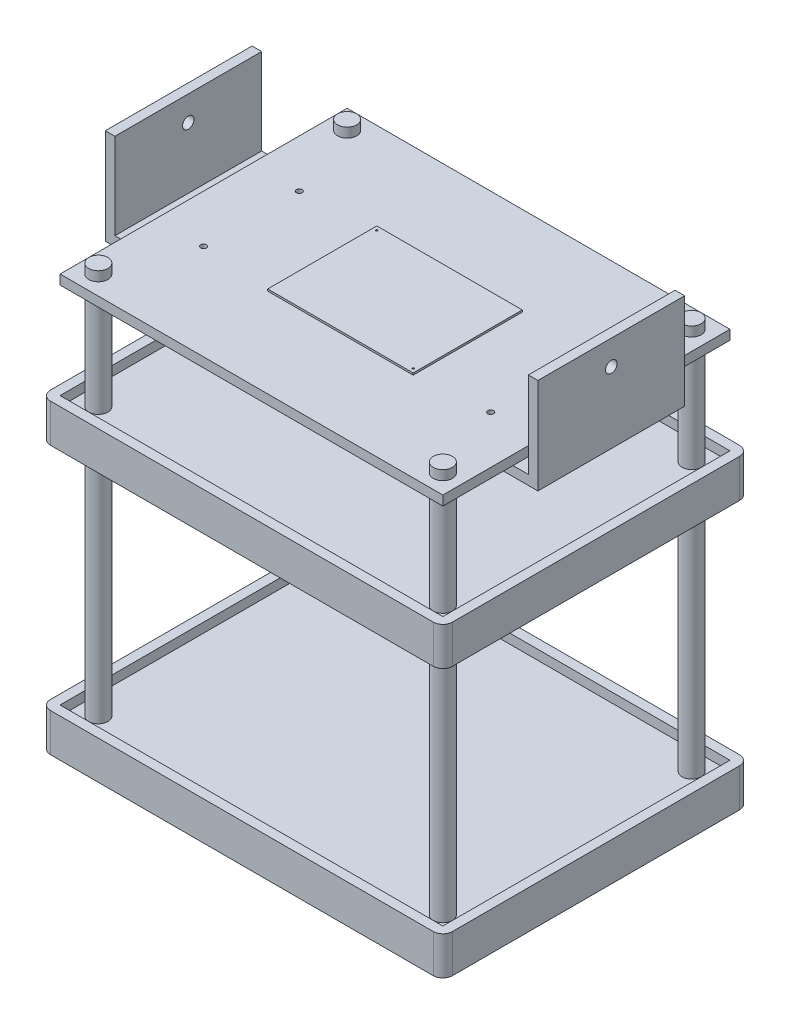
SolidWorks part; units mm, degrees
ref_plane "Front Plane" through (0, 0, 0) normal (0, 0, 1) x (1, 0, 0)
ref_plane "Top Plane" through (0, 0, 0) normal (0, 1, 0) x (1, 0, 0)
ref_plane "Right Plane" through (0, 0, 0) normal (1, 0, 0) x (0, 0, -1)
sketch "Sketch1" plane through (0, 0, 0) normal (0, 1, 0) x (1, 0, 0)
  line L1 (-100, 75) -> (100, 75)
  line L2 (-100, 75) -> (-100, -75)
  line L3 (-100, -75) -> (100, -75)
  line L4 (100, 75) -> (100, -75)
  line L5 (-100, 75) -> (100, -75) construction
  line L6 (-100, -75) -> (100, 75) construction
  point P0 (0, 0)
  dimension "D1" = 200
  dimension "D2" = 150
extrude "Boss-Extrude1" add sketch "Sketch1" along normal blind 5
sketch "Sketch2" plane through (0, 5, 0) normal (0, 1, 0) x (1, 0, 0)
  line L0 (-100, 75) -> (-100, -75) construction
  line L1 (100, 75) -> (-100, 75) construction
  line L2 (0, 73.0671) -> (0, 83.6614) construction
  line L3 (0, 83.6614) -> (0, -94.4748) construction
  line L4 (-110.8687, 0) -> (113.9791, 0) construction
  circle A0 centre (-90, 65) radius 5
  circle A1 centre (90, 65) radius 5
  circle A2 centre (90, -65) radius 5
  circle A3 centre (-90, -65) radius 5
  dimension "D1" = 10
  dimension "D2" = 10
  dimension "D3" = 10
extrude "Cut-Extrude1" cut sketch "Sketch2" against normal blind 10
ref_plane "Plane1" through (0, 140, 0) normal (0, 1, 0) x (1, 0, 0)
sketch "Sketch3" plane through (0, 140, 0) normal (0, 1, 0) x (1, 0, 0)
  line L1 (-100, 75) -> (100, 75)
  line L2 (-100, 75) -> (-100, -75)
  line L3 (-100, -75) -> (100, -75)
  line L4 (100, 75) -> (100, -75)
  line L5 (-100, 75) -> (100, -75) construction
  line L6 (-100, -75) -> (100, 75) construction
  circle A0 centre (-90, 65) radius 5
  circle A1 centre (90, 65) radius 5
  circle A2 centre (-90, -65) radius 5
  circle A3 centre (90, -65) radius 5
  point P0 (0, 0)
extrude "Boss-Extrude2" add sketch "Sketch3" along normal blind 5 separate body
ref_plane "Plane4" through (0, 200, 0) normal (0, 1, 0) x (1, 0, 0)
sketch "Sketch4" plane through (0, 200, 0) normal (0, 1, 0) x (1, 0, 0)
  line L1 (-100, 75) -> (100, 75)
  line L2 (-100, 75) -> (-100, -75)
  line L3 (-100, -75) -> (100, -75)
  line L4 (100, 75) -> (100, -75)
  line L5 (-100, 75) -> (100, -75) construction
  line L6 (-100, -75) -> (100, 75) construction
  circle A0 centre (-90, 65) radius 5
  circle A1 centre (90, 65) radius 5
  circle A2 centre (90, -65) radius 5
  circle A3 centre (-90, -65) radius 5
  point P1 (0, 0)
extrude "Boss-Extrude3" add sketch "Sketch4" along normal blind 5 separate body
sketch "Sketch5" plane through (0, 205, 0) normal (0, 1, 0) x (1, 0, 0)
  circle A0 centre (-90, -65) radius 5
sketch "Sketch17" plane through (0, 200, 0) normal (0, -1, 0) x (1, 0, 0)
  circle A0 centre (-90, -65) radius 5.3637
sketch "Sketch21" plane through (0, 5, 0) normal (0, 1, 0) x (1, 0, 0)
  circle A0 centre (-90, -65) radius 5
  circle A1 centre (-90, 65) radius 5
  circle A2 centre (90, 65) radius 5
  circle A3 centre (90, -65) radius 5
  dimension "D1" = 10
  dimension "D2" = 10
  dimension "D3" = 10
  dimension "D4" = 10
extrude "Boss-Extrude13" add sketch "Sketch21" along normal blind 205
sketch "Sketch22" plane through (0, 5, 0) normal (0, 1, 0) x (1, 0, 0)
  circle A0 centre (-90, 65) radius 5
  circle A1 centre (-90, -65) radius 5
  circle A2 centre (90, -65) radius 5
  circle A3 centre (90, 65) radius 5
  dimension "D1" = 10
  dimension "D2" = 10
  dimension "D3" = 10
  dimension "D4" = 10
extrude "Boss-Extrude14" add sketch "Sketch22" against normal blind 15
sketch "Sketch23" plane through (0, 205, 0) normal (0, 1, 0) x (1, 0, 0)
  line L0 (-100, 75) -> (-100, -75) construction
  line L1 (-140.155, 0) -> (119.4256, 0) construction
  line L2 (0, -2.75) -> (0, 2.75) construction
  circle A0 centre (-75, 25) radius 1.5
  circle A1 centre (-75, -25) radius 1.5
  circle A2 centre (75, -25) radius 1.5
  circle A3 centre (75, 25) radius 1.5
  dimension "D1" = 3
  dimension "D2" = 25
  dimension "D3" = 25
extrude "Cut-Extrude2" cut sketch "Sketch23" against normal blind 10
sketch "Sketch27" plane through (0, 205, 0) normal (0, 1, 0) x (1, 0, 0)
  line L0 (-38, 28.5) -> (38, -28.5) construction
  line L5 (-38, -28.5) -> (38, 28.5) construction
  line L7 (-38, 28.5) -> (38, 28.5)
  line L8 (-38, 28.5) -> (-38, -28.5)
  line L9 (-38, -28.5) -> (38, -28.5)
  line L10 (38, 28.5) -> (38, -28.5)
  circle A0 centre (-36, 26.5) radius 0.5
  circle A1 centre (36, -26.5) radius 0.5
  point P0 (-6.164, -10.787)
  point P5 (0, 0)
  point P11 (0, 0)
  dimension "D3" = 1
  dimension "D6" = 1
  dimension "D1" = 57
  dimension "D2" = 76
  dimension "D4" = 2
  dimension "D5" = 2
  dimension "D7" = 2
  dimension "D8" = 2
extrude "Boss-Extrude16" add sketch "Sketch27" along normal blind 1 contours L8 L7 L10 L9
sketch "Sketch30" plane through (0, 206, 0) normal (0, 1, 0) x (1, 0, 0)
  line L0 (-38, 28.5) -> (-38, -28.5) construction
  line L1 (-38, 28.5) -> (38, 28.5) construction
  line L2 (38, 28.5) -> (38, -28.5) construction
  line L3 (-38, -28.5) -> (38, -28.5) construction
  circle A0 centre (-36, 26.5) radius 0.5
  circle A1 centre (36, -26.5) radius 0.5
  dimension "D1" = 1
  dimension "D4" = 1
  dimension "D2" = 2
  dimension "D3" = 2
  dimension "D5" = 2
  dimension "D6" = 2
extrude "Cut-Extrude3" cut sketch "Sketch30" against normal blind 30
sketch "Sketch35" plane through (0, 0, 0) normal (0, -1, 0) x (-1, 0, 0)
  line L1 (100, -75) -> (-100, -75)
  line L2 (100, -75) -> (100, 75)
  line L3 (100, 75) -> (-100, 75)
  line L4 (-100, -75) -> (-100, 75)
  line L5 (100, -75) -> (-100, 75) construction
  line L6 (100, 75) -> (-100, -75) construction
  line L7 (105, -80) -> (-105, -80)
  line L8 (105, -80) -> (105, 80)
  line L9 (105, 80) -> (-105, 80)
  line L10 (-105, -80) -> (-105, 80)
  line L11 (105, -80) -> (-105, 80) construction
  line L12 (105, 80) -> (-105, -80) construction
  point P0 (0, 0)
  point P6 (0, 0)
  dimension "D1" = 150
  dimension "D2" = 160
  dimension "D3" = 200
  dimension "D4" = 210
extrude "Boss-Extrude19" add sketch "Sketch35" along normal mid plane 20 separate body
fillet "Fillet4" radius 5 4 edges at (105, 0, 80) (105, 0, -80) (-105, 0, 80) (-105, 0, -80)
sketch "Sketch39" plane through (0, 140, 0) normal (0, -1, 0) x (1, 0, 0)
  line L1 (-100, 75) -> (100, 75)
  line L2 (-100, 75) -> (-100, -75)
  line L3 (-100, -75) -> (100, -75)
  line L4 (100, 75) -> (100, -75)
  line L5 (-100, 75) -> (100, -75) construction
  line L6 (-100, -75) -> (100, 75) construction
  line L7 (-105, 80) -> (105, 80)
  line L8 (-105, 80) -> (-105, -80)
  line L9 (-105, -80) -> (105, -80)
  line L10 (105, 80) -> (105, -80)
  line L11 (-105, 80) -> (105, -80) construction
  line L12 (-105, -80) -> (105, 80) construction
  point P0 (0, 0)
  point P6 (0, 0)
  dimension "D1" = 150
  dimension "D2" = 200
  dimension "D3" = 160
  dimension "D4" = 210
extrude "Boss-Extrude20" add sketch "Sketch39" along normal mid plane 20 separate body
fillet "Fillet5" radius 5 4 edges at (105, 140, 80) (105, 140, -80) (-105, 140, -80) (-105, 140, 80)
sketch "Sketch42" plane through (0, 200, 0) normal (0, -1, 0) x (1, 0, 0)
  line L1 (-7.5, 10) -> (7.5, 10)
  line L2 (-7.5, 10) -> (-7.5, -10)
  line L3 (-7.5, -10) -> (7.5, -10)
  line L4 (7.5, 10) -> (7.5, -10)
  line L5 (-7.5, 10) -> (7.5, -10) construction
  line L6 (-7.5, -10) -> (7.5, 10) construction
  line L7 (-70.7403, -17.1967) -> (-45.7403, -17.1967)
  line L8 (-70.7403, -17.1967) -> (-70.7403, 32.8033)
  line L9 (-70.7403, 32.8033) -> (-45.7403, 32.8033)
  line L10 (-45.7403, -17.1967) -> (-45.7403, 32.8033)
  line L11 (-70.7403, -17.1967) -> (-45.7403, 32.8033) construction
  line L12 (-70.7403, 32.8033) -> (-45.7403, -17.1967) construction
  line L13 (15.7, 23.8618) -> (59, 23.8618)
  line L14 (15.7, 23.8618) -> (15.7, -19.4382)
  line L15 (15.7, -19.4382) -> (59, -19.4382)
  line L16 (59, 23.8618) -> (59, -19.4382)
  line L17 (15.7, 23.8618) -> (59, -19.4382) construction
  line L18 (15.7, -19.4382) -> (59, 23.8618) construction
  point P0 (0, 0)
  point P6 (-58.2403, 7.8033)
  point P11 (37.35, 2.2118)
  dimension "D1" = 20
  dimension "D2" = 15
  dimension "D3" = 50
  dimension "D4" = 25
  dimension "D5" = 43.3
  dimension "D6" = 43.3
  dimension "D7" = 8.2
extrude "Boss-Extrude23" add sketch "Sketch42" along normal blind 1
sketch "Sketch46" plane through (0, 200, 0) normal (0, -1, 0) x (-1, 0, 0)
  line L0 (-196.0871, 0) -> (303.0775, 0) construction
  line L5 (100, -75) -> (100, 75) construction
  line L6 (0, 82.5) -> (0, -82.5) construction
  line L7 (-108, 38.3353) -> (-108, -38.3353)
  line L8 (78, 38.3353) -> (108, 38.3353)
  line L9 (78, 38.3353) -> (78, -38.3353)
  line L10 (78, -38.3353) -> (108, -38.3353)
  line L11 (108, 38.3353) -> (108, -38.3353)
  line L12 (78, 38.3353) -> (108, -38.3353) construction
  line L13 (78, -38.3353) -> (108, 38.3353) construction
  line L14 (-78, -38.3353) -> (-108, -38.3353)
  line L15 (-78, 38.3353) -> (-78, -38.3353)
  line L16 (-78, 38.3353) -> (-108, 38.3353)
  point P0 (122.8294, -19.1676)
  point P6 (93, 0)
  dimension "D1" = 22
  dimension "D2" = 30
extrude "Boss-Extrude24" add sketch "Sketch46" along normal blind 5
sketch "Sketch48" plane through (-108, 0, 0) normal (-1, 0, 0) x (0, 0, 1)
  line L1 (-38.3353, 195) -> (38.3353, 195)
  line L2 (-38.3353, 195) -> (-38.3353, 245)
  line L3 (-38.3353, 245) -> (38.3353, 245)
  line L4 (38.3353, 195) -> (38.3353, 245)
  dimension "D1" = 50
extrude "Boss-Extrude25" add sketch "Sketch48" along normal blind 5
sketch "Sketch49" plane through (-113, 0, 0) normal (-1, 0, 0) x (0, 0, 1)
  line L1 (-38.3353, 195) -> (38.3353, 195) construction
  circle A0 centre (0, 232) radius 3
  dimension "D2" = 6
  dimension "D1" = 37
extrude "Cut-Extrude4" cut sketch "Sketch49" against normal blind 5
sketch "Sketch54" plane through (108, 0, 0) normal (1, 0, 0) x (0, 0, -1)
  line L1 (-38.3353, 195) -> (38.3353, 195)
  line L2 (-38.3353, 195) -> (-38.3353, 245)
  line L3 (-38.3353, 245) -> (38.3353, 245)
  line L4 (38.3353, 195) -> (38.3353, 245)
extrude "Boss-Extrude26" add sketch "Sketch54" along normal blind 5
sketch "Sketch55" plane through (113, 0, 0) normal (1, 0, 0) x (0, 0, -1)
  line L0 (-38.3353, 195) -> (38.3353, 195) construction
  circle A0 centre (0, 232) radius 3
  dimension "D1" = 6
  dimension "D2" = 37
extrude "Cut-Extrude5" cut sketch "Sketch55" against normal blind 5
